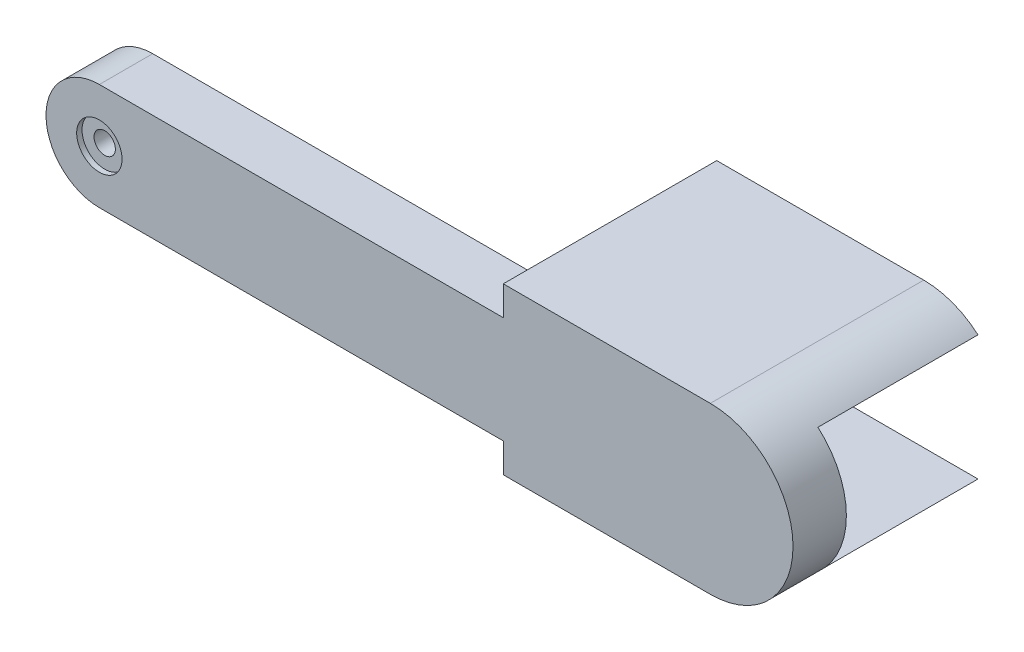
SolidWorks part; units mm, degrees
ref_plane "Front" through (0, 0, 0) normal (0, 0, 1) x (1, 0, 0)
ref_plane "Top" through (0, 0, 0) normal (0, 1, 0) x (1, 0, 0)
ref_plane "Right" through (0, 0, 0) normal (1, 0, 0) x (0, 0, -1)
sketch "Sketch1" plane through (0, 0, 0) normal (0, 0, 1) x (1, 0, 0)
  line L0 (0, 0) -> (60, 0) construction
  line L1 (0, 5) -> (60, 5)
  line L2 (0, -5) -> (60, -5)
  arc A1 (0, 5) -> (0, -5) centre (0, 0) ccw
  arc A2 (60, -5) -> (60, 5) centre (60, 0) ccw
  point P3 (30, 0)
  dimension "D1" = 5
  dimension "D2" = 60
extrude "Boss-Extrude1" add sketch "Sketch1" along normal blind 5 contours A1 L2 A2 L1
sketch "Sketch2" plane through (0, 0, 0) normal (0, 0, -1) x (-1, 0, 0)
  line L0 (0, 0) -> (2.35, 0) construction
  line L1 (2.25, 0) -> (2.3443, 0.1634)
  line L2 (2.25, 0) -> (2.3443, -0.1634)
  line L3 (2.1399, -0.6953) -> (2.2801, -0.5691)
  line L4 (2.1399, -0.6953) -> (2.1791, -0.8798)
  line L5 (1.8203, -1.3225) -> (1.9926, -1.2458)
  line L6 (1.8203, -1.3225) -> (1.8006, -1.5101)
  line L7 (1.3225, -1.8203) -> (1.5101, -1.8006)
  line L8 (1.3225, -1.8203) -> (1.2458, -1.9926)
  line L9 (0.6953, -2.1399) -> (0.8798, -2.1791)
  line L10 (0.6953, -2.1399) -> (0.5691, -2.2801)
  line L11 (0, -2.25) -> (0.1634, -2.3443)
  line L12 (0, -2.25) -> (-0.1634, -2.3443)
  line L13 (-0.6953, -2.1399) -> (-0.5691, -2.2801)
  line L14 (-0.6953, -2.1399) -> (-0.8798, -2.1791)
  line L15 (-1.3225, -1.8203) -> (-1.2458, -1.9926)
  line L16 (-1.3225, -1.8203) -> (-1.5101, -1.8006)
  line L17 (-1.8203, -1.3225) -> (-1.8006, -1.5101)
  line L18 (-1.8203, -1.3225) -> (-1.9926, -1.2458)
  line L19 (-2.1399, -0.6953) -> (-2.1791, -0.8798)
  line L20 (-2.1399, -0.6953) -> (-2.2801, -0.5691)
  line L21 (-2.25, 0) -> (-2.3443, -0.1634)
  line L22 (-2.25, 0) -> (-2.3443, 0.1634)
  line L23 (-2.1399, 0.6953) -> (-2.2801, 0.5691)
  line L24 (-2.1399, 0.6953) -> (-2.1791, 0.8798)
  line L25 (-1.8203, 1.3225) -> (-1.9926, 1.2458)
  line L26 (-1.8203, 1.3225) -> (-1.8006, 1.5101)
  line L27 (-1.3225, 1.8203) -> (-1.5101, 1.8006)
  line L28 (-1.3225, 1.8203) -> (-1.2458, 1.9926)
  line L29 (-0.6953, 2.1399) -> (-0.8798, 2.1791)
  line L30 (-0.6953, 2.1399) -> (-0.5691, 2.2801)
  line L31 (0, 2.25) -> (-0.1634, 2.3443)
  line L32 (0, 2.25) -> (0.1634, 2.3443)
  line L33 (0.6953, 2.1399) -> (0.5691, 2.2801)
  line L34 (0.6953, 2.1399) -> (0.8798, 2.1791)
  line L35 (1.3225, 1.8203) -> (1.2458, 1.9926)
  line L36 (1.3225, 1.8203) -> (1.5101, 1.8006)
  line L37 (1.8203, 1.3225) -> (1.8006, 1.5101)
  line L38 (1.8203, 1.3225) -> (1.9926, 1.2458)
  line L39 (2.1399, 0.6953) -> (2.1791, 0.8798)
  line L40 (2.1399, 0.6953) -> (2.2801, 0.5691)
  circle A0 centre (0, 0) radius 2.35
  arc A1 (2.3443, -0.1634) -> (2.3443, 0.1634) centre (0, 0) ccw
  arc A2 (2.1791, -0.8798) -> (2.2801, -0.5691) centre (0, 0) ccw
  arc A3 (1.8006, -1.5101) -> (1.9926, -1.2458) centre (0, 0) ccw
  arc A4 (1.2458, -1.9926) -> (1.5101, -1.8006) centre (0, 0) ccw
  arc A5 (0.5691, -2.2801) -> (0.8798, -2.1791) centre (0, 0) ccw
  arc A6 (-0.1634, -2.3443) -> (0.1634, -2.3443) centre (0, 0) ccw
  arc A7 (-0.8798, -2.1791) -> (-0.5691, -2.2801) centre (0, 0) ccw
  arc A8 (-1.5101, -1.8006) -> (-1.2458, -1.9926) centre (0, 0) ccw
  arc A9 (-1.9926, -1.2458) -> (-1.8006, -1.5101) centre (0, 0) ccw
  arc A10 (-2.2801, -0.5691) -> (-2.1791, -0.8798) centre (0, 0) ccw
  arc A11 (-2.3443, 0.1634) -> (-2.3443, -0.1634) centre (0, 0) ccw
  arc A12 (-2.1791, 0.8798) -> (-2.2801, 0.5691) centre (0, 0) ccw
  arc A13 (-1.8006, 1.5101) -> (-1.9926, 1.2458) centre (0, 0) ccw
  arc A14 (-1.2458, 1.9926) -> (-1.5101, 1.8006) centre (0, 0) ccw
  arc A15 (-0.5691, 2.2801) -> (-0.8798, 2.1791) centre (0, 0) ccw
  arc A16 (0.1634, 2.3443) -> (-0.1634, 2.3443) centre (0, 0) ccw
  arc A17 (0.8798, 2.1791) -> (0.5691, 2.2801) centre (0, 0) ccw
  arc A18 (1.5101, 1.8006) -> (1.2458, 1.9926) centre (0, 0) ccw
  arc A19 (1.9926, 1.2458) -> (1.8006, 1.5101) centre (0, 0) ccw
  arc A20 (2.2801, 0.5691) -> (2.1791, 0.8798) centre (0, 0) ccw
  point P67 (0, 0)
  dimension "D1" = 4.7
  dimension "D3" = 20
  dimension "D2" = 0.1
  dimension "D4" = 120
extrude "Cut-Extrude1" cut sketch "Sketch2" against normal blind 3 contours L1 A0 L40 L39 L38 L37 L36 L35 L34 L33 L32 L31 L30 L29 L28 L27 L26 L25 L24 L23 L22 L21 L20 L19 L18 L17 L16 L15 L14 L13 L12 L11 L10 L9 L8 region at (0, 0, 0)
sketch "Sketch3" plane through (0, 0, 5) normal (0, 0, 1) x (1, 0, 0)
  circle A0 centre (0, 0) radius 2.125
  dimension "D1" = 4.25
extrude "Cut-Extrude2" cut sketch "Sketch3" against normal blind 0.5
sketch "Sketch4" plane through (0, 0, 4.5) normal (0, 0, 1) x (1, 0, 0)
  circle A0 centre (0, 0) radius 1
  dimension "D1" = 2
extrude "Cut-Extrude3" cut sketch "Sketch4" against normal through all
ref_axis "Axis1" through (60, 0, 5) along (0, 0, -1)
sketch "Sketch5" plane through (0, 0, 0) normal (0, 0, -1) x (-1, 0, 0)
  line L0 (-37.85, 5) -> (-37.85, 7.75)
  line L1 (0, 5) -> (-60, 5) construction
  line L2 (-37.85, 7.75) -> (-57.25, 7.75)
  line L3 (-37.85, -5) -> (-37.85, -7.75)
  line L4 (0, -5) -> (-60, -5) construction
  line L5 (-37.85, -7.75) -> (-57.25, -7.75)
  line L6 (-60, 5) -> (-37.85, 5)
  line L7 (-60, -5) -> (-37.85, -5)
  line L8 (-41.95, -5.75) -> (-65.75, -5.75) construction
  line L9 (-41.95, -5.75) -> (-65.75, -5.75) construction
  line L10 (-37.85, -5.75) -> (-37.85, 5.75) construction
  line L11 (-37.85, -5.75) -> (-37.85, 5.75) construction
  arc A0 (-60, 5) -> (-60, -5) centre (-60, 0) ccw construction
  arc A1 (-60, 5) -> (-60, -5) centre (-60, 0) ccw
  arc A2 (-57.25, 7.75) -> (-65, 0) centre (-57.25, 0) ccw
  arc A3 (-57.25, -7.75) -> (-65, 0) centre (-57.25, 0) cw
  dimension "D1" = 2
extrude "Boss-Extrude2" add sketch "Sketch5" against normal up to surface (5 mm away) contours L2 A2 L0 | A3 L5 L3 A1 region at (50.1467, 6.2442, 0) region at (50.1467, -6.2442, 0) up to face at (2.125, 0, 5)
sketch "Sketch6" plane through (0, 0, 0) normal (0, 0, -1) x (-1, 0, 0)
  line L0 (-62.3333, -5.85) -> (-41.85, -5.85)
  line L1 (-41.85, -5.85) -> (-41.85, 5.85)
  line L2 (-41.85, 5.85) -> (-62.3333, 5.85)
  line L3 (-37.85, -5) -> (-37.85, 5)
  line L4 (-37.85, 5) -> (-37.85, 7.75) construction
  line L5 (-37.85, -5) -> (-37.85, -7.75) construction
  line L6 (-37.85, 5) -> (-37.85, 7.75)
  line L7 (-37.85, -5) -> (-37.85, -7.75)
  line L8 (-37.85, 7.75) -> (-57.25, 7.75) construction
  line L9 (-37.85, -7.75) -> (-57.25, -7.75) construction
  line L10 (-37.85, 7.75) -> (-57.25, 7.75)
  line L11 (-37.85, -7.75) -> (-57.25, -7.75)
  line L12 (-41.95, -5.75) -> (-65.75, -5.75) construction
  line L13 (-41.95, 5.75) -> (-65.75, 5.75) construction
  line L14 (-41.95, 5.75) -> (-41.95, -5.75) construction
  arc A0 (-57.25, 7.75) -> (-57.25, -7.75) centre (-57.25, 0) ccw construction
  arc A1 (-57.25, 7.75) -> (-62.3333, 5.85) centre (-57.25, 0) ccw
  arc A2 (-57.25, -7.75) -> (-62.3333, -5.85) centre (-57.25, 0) cw
  dimension "D1" = 0.1
  dimension "D2" = 0.1
  dimension "D3" = 0.1
extrude "Boss-Extrude3" add sketch "Sketch6" along normal up to surface (15 mm away) up to face at (33.5812, 0, 5)
sketch "Sketch10" plane through (0, 0, -15) normal (0, 0, -1) x (-1, 0, 0)
  circle A0 centre (-39.9, 0) radius 1.125 construction
  circle A1 centre (-39.9, 0) radius 1.125 construction
  circle A2 centre (-39.9, 0) radius 0.875
  dimension "D1" = 1.75
extrude "Cut-Extrude6" cut sketch "Sketch10" against normal blind 6 contours A2
equation "\"LENGTH\"= 60mm"
equation "\"D2@Sketch1\"=\"LENGTH\""
